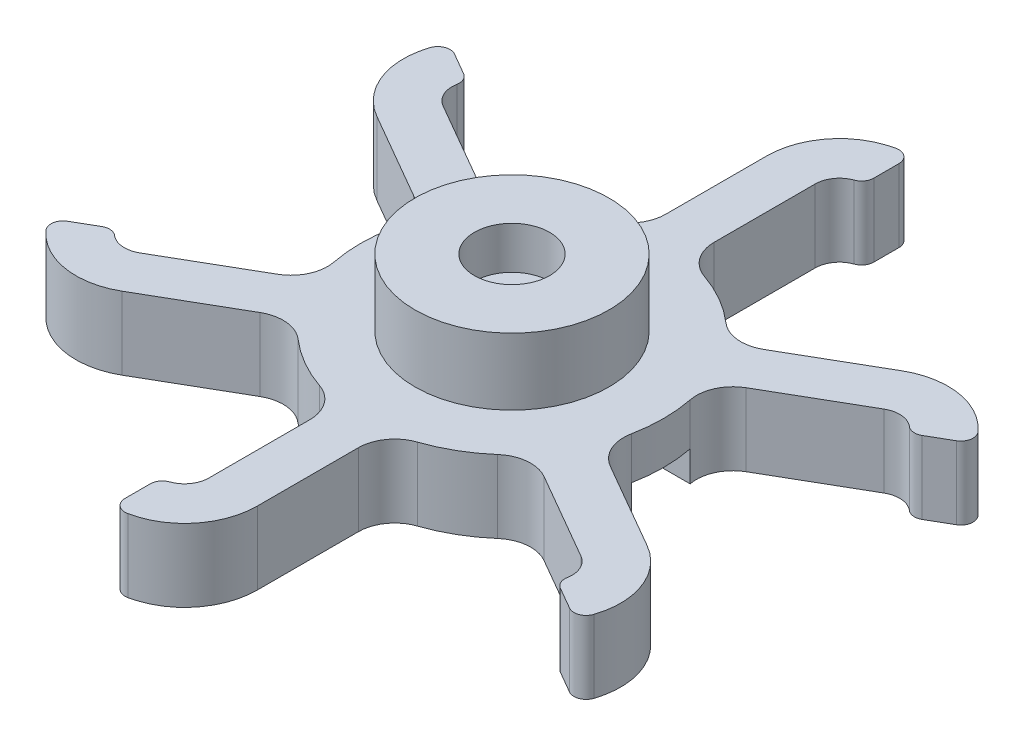
SolidWorks part; units mm, degrees
ref_plane "Front" through (0, 0, 0) normal (0, 0, 1) x (1, 0, 0)
ref_plane "Top" through (0, 0, 0) normal (0, 1, 0) x (1, 0, 0)
ref_plane "Right" through (0, 0, 0) normal (1, 0, 0) x (0, 0, -1)
sketch "草图1" plane through (0, 0, 0) normal (0, 1, 0) x (1, 0, 0)
  line L0 (0, 12.5) -> (0, 23) construction
  line L1 (2, 23) -> (2, 12.339)
  line L2 (18.9186, 13.2321) -> (9.6859, 7.9015)
  line L3 (20.9186, 9.7679) -> (11.6859, 4.4374)
  line L4 (20.9186, -9.7679) -> (11.6859, -4.4374)
  line L5 (18.9186, -13.2321) -> (9.6859, -7.9015)
  line L6 (2, -23) -> (2, -12.339)
  line L7 (-2, 23) -> (-2, 12.339)
  line L8 (-2, -23) -> (-2, -12.339)
  line L9 (-18.9186, -13.2321) -> (-9.6859, -7.9015)
  line L10 (-20.9186, -9.7679) -> (-11.6859, -4.4374)
  line L11 (-20.9186, 9.7679) -> (-11.6859, 4.4374)
  line L12 (-18.9186, 13.2321) -> (-9.6859, 7.9015)
  line L13 (0, 0) -> (2, 12.339) construction
  line L14 (4, 29) -> (4, 25)
  line L15 (27.1147, 11.0359) -> (23.6506, 9.0359)
  line L16 (23.1147, -17.9641) -> (19.6506, -15.9641)
  line L17 (-4, -29) -> (-4, -25)
  line L18 (-27.1147, -11.0359) -> (-23.6506, -9.0359)
  line L19 (-23.1147, 17.9641) -> (-19.6506, 15.9641)
  line L20 (0, 0) -> (2, 23) construction
  circle A0 centre (0, 0) radius 12.5
  arc A1 (-2, 23) -> (4, 29) centre (4, 23) cw
  arc A2 (2, 23) -> (4, 25) centre (4, 23) cw
  arc A3 (20.9186, 9.7679) -> (23.6506, 9.0359) centre (21.9186, 8.0359) cw
  arc A4 (18.9186, 13.2321) -> (27.1147, 11.0359) centre (21.9186, 8.0359) cw
  arc A5 (18.9186, -13.2321) -> (19.6506, -15.9641) centre (17.9186, -14.9641) cw
  arc A6 (20.9186, -9.7679) -> (23.1147, -17.9641) centre (17.9186, -14.9641) cw
  arc A7 (-2, -23) -> (-4, -25) centre (-4, -23) cw
  arc A8 (2, -23) -> (-4, -29) centre (-4, -23) cw
  arc A9 (-20.9186, -9.7679) -> (-23.6506, -9.0359) centre (-21.9186, -8.0359) cw
  arc A10 (-18.9186, -13.2321) -> (-27.1147, -11.0359) centre (-21.9186, -8.0359) cw
  arc A11 (-18.9186, 13.2321) -> (-19.6506, 15.9641) centre (-17.9186, 14.9641) cw
  arc A12 (-20.9186, 9.7679) -> (-23.1147, 17.9641) centre (-17.9186, 14.9641) cw
  dimension "D1" = 25
  dimension "D6" = 6
  dimension "D7" = 2
  dimension "D2" = 10.5
  dimension "D4" = 12.5
  dimension "D5" = 2
  dimension "D9" = 23.0868
  dimension "D10" = 19.6506
  dimension "D3" = 6
  dimension "D8" = 6
extrude "凸台-拉伸1" add sketch "草图1" along normal blind 6 contours A0 | A6 L4 A0 L5 A5 L16 | A8 L6 A0 L8 A7 L17 | A10 L9 A0 L10 A9 L18 | A4 L2 A0 L3 A3 L15 | L1 A2 L14 A1 L7 A0 | A12 L11 A0 L12 A11 L19 region at (0.4632, 0, -20.7219) region at (0, 0, 0) region at (18.1773, 0, -9.9598) region at (-17.714, 0, -10.7621) region at (17.714, 0, 10.7621) region at (-18.1773, 0, 9.9598) region at (-0.4632, 0, 20.7219)
fillet "圆角1" radius 3 12 edges at (9.6859, 3, -7.9015) (2, 3, -12.339) (-2, 3, -12.339) (-9.6859, 3, -7.9015) (-11.6859, 3, -4.4374) (-11.6859, 3, 4.4374) (-9.6859, 3, 7.9015) (-2, 3, 12.339) (2, 3, 12.339) (11.6859, 3, 4.4374) (9.6859, 3, 7.9015) (11.6859, 3, -4.4374)
fillet "圆角2" radius 1 12 edges at (-4, 3, 25) (-27.1147, 3, 11.0359) (-23.6506, 3, 9.0359) (-23.1147, 3, -17.9641) (-19.6506, 3, -15.9641) (4, 3, -29) (4, 3, -25) (27.1147, 3, -11.0359) (23.6506, 3, -9.0359) (19.6506, 3, 15.9641) (23.1147, 3, 17.9641) (-4, 3, 29)
sketch "草图2" plane through (0, 0, 0) normal (0, 1, 0) x (1, 0, 0)
  circle A0 centre (0, 0) radius 8
  dimension "D1" = 16
extrude "凸台-拉伸2" add sketch "草图2" against normal blind 2.5
sketch "草图3" plane through (0, -2.5, 0) normal (0, -1, 0) x (-1, 0, 0)
  circle A0 centre (0, 0) radius 3.1
  dimension "D1" = 6.2
extrude "切除-拉伸1" cut sketch "草图3" against normal through all
sketch "草图5" plane through (0, 6, 0) normal (0, 1, 0) x (1, 0, 0)
  circle A0 centre (0, 0) radius 3.1
  circle A1 centre (0, 0) radius 8
  dimension "D1" = 6.2
  dimension "D2" = 16
extrude "凸台-拉伸3" add sketch "草图5" along normal blind 1.5
sketch "草图6" plane through (0, 7.5, 0) normal (0, 1, 0) x (1, 0, 0)
  circle A0 centre (0, 0) radius 8
  circle A1 centre (0, 0) radius 1.25
  dimension "D1" = 2.5
  dimension "D2" = 16
extrude "凸台-拉伸4" add sketch "草图6" along normal blind 0.5
cosmetic thread "装饰螺纹线4" [suppressed] parameters "D2"=3
sketch "草图7" plane through (0, 8, 0) normal (0, 1, 0) x (1, 0, 0)
  circle A0 centre (0, 0) radius 8
  circle A1 centre (0, 0) radius 3.1
  dimension "D1" = 6.2
  dimension "D2" = 16
extrude "凸台-拉伸5" add sketch "草图7" along normal blind 3.5
extrude "凸台-拉伸6" add sketch "草图6<2>" against normal blind 3.2
sketch "草图6<2>" plane through (0, 7.5, 0) normal (0, 1, 0) x (1, 0, 0) same geometry as "草图6"
ref_plane "基准面2" through (7, 0, 0) normal (1, 0, 0) x (0, 0, -1)
sketch "草图12" plane through (7, 0, 0) normal (1, 0, 0) x (0, 0, -1)
  line L0 (-3.1, -2.5) -> (3.1, -2.5) construction
  line L1 (-8, 0) -> (8, 0)
  line L2 (-8, 0) -> (-8, -5)
  line L3 (-8, -5) -> (8, -5)
  line L4 (8, 0) -> (8, -5)
  line L5 (0, -5) -> (0, 0) construction
  line L6 (-8, -2.5) -> (8, -2.5) construction
  line L7 (-8, 0) -> (8, 0) construction
  point P0 (0, -2.5)
  dimension "D1" = 16
extrude "切除-拉伸7" cut sketch "草图12" along normal through all
sketch "草图16" plane through (0, -2.5, 0) normal (0, -1, 0) x (1, 0, 0)
  line L1 (2.7, 2) -> (3.5, 2)
  line L2 (2.7, 2) -> (2.7, -2)
  line L3 (2.7, -2) -> (3.5, -2)
  line L4 (3.5, 2) -> (3.5, -2)
  line L5 (3.1, -2) -> (3.1, 2) construction
  line L6 (2.7, 0) -> (3.5, 0) construction
  circle A0 centre (0, 0) radius 3.1 construction
  point P0 (3.1, 0)
  dimension "D1" = 2.7
  dimension "4" = 4
extrude "凸台-拉伸7" add sketch "草图16" against normal up to next
sketch "草图14" plane through (0, 0, 0) normal (1, 0, 0) x (0, 0, -1)
  circle A0 centre (0, 0) radius 1.25
  dimension "D1" = 2.5
extrude "切除-拉伸8" cut sketch "草图14" along normal through all
cosmetic thread "装饰螺纹线5" parameters "D2"=3
sketch "草图15" plane through (7, 0, 0) normal (1, 0, 0) x (0, 0, -1)
  line L0 (-3.1, -2.5) -> (3.1, -2.5) construction
  line L1 (-2.4238, 2.5) -> (2.4238, 2.5)
  line L2 (-2.4238, 2.5) -> (-2.4238, -2.5)
  line L3 (-2.4238, -2.5) -> (2.4238, -2.5)
  line L4 (2.4238, 2.5) -> (2.4238, -2.5)
  line L5 (0, -2.5) -> (0, 2.5) construction
  line L6 (-2.4238, 0) -> (2.4238, 0) construction
  line L7 (2.4238, 0) -> (2.4238, 6) construction
  point P0 (0, 0)
extrude "切除-拉伸9" cut sketch "草图15" along normal through all
sketch "草图17" plane through (0, 8, 0) normal (0, 1, 0) x (1, 0, 0)
  circle A0 centre (0, 0) radius 1.55
  dimension "D1" = 3.1
extrude "切除-拉伸10" cut sketch "草图17" against normal up to next
mirror "镜向1" [suppressed] about plane through (7, 0, 0) normal (1, 0, 0) of bodies 119
